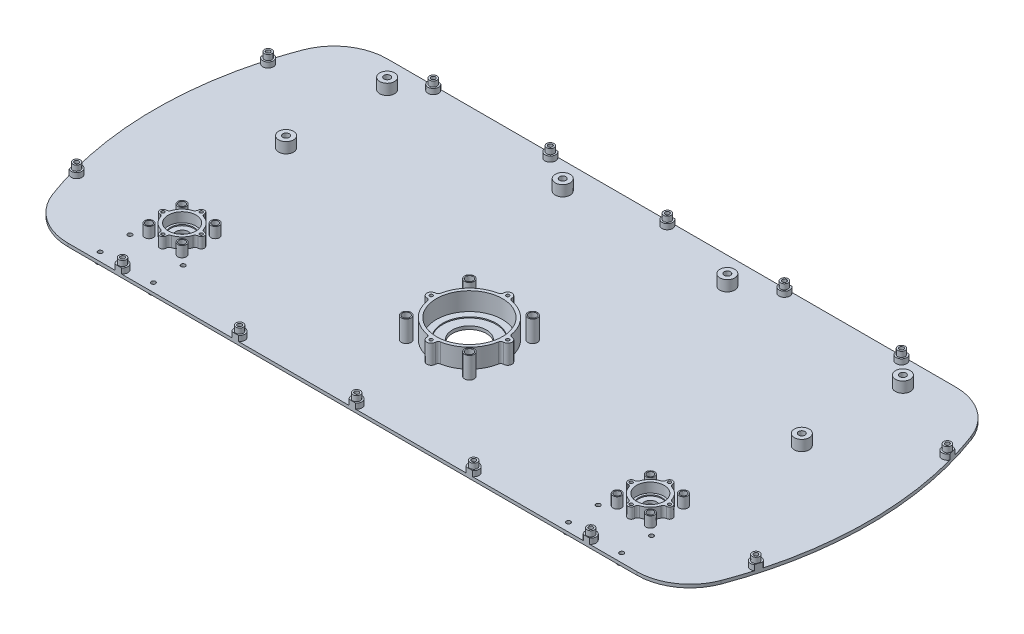
SolidWorks part; units mm, degrees
ref_plane "Front Plane" through (0, 0, 0) normal (0, 0, 1) x (1, 0, 0)
ref_plane "Top Plane" through (0, 0, 0) normal (0, 1, 0) x (1, 0, 0)
ref_plane "Right Plane" through (0, 0, 0) normal (1, 0, 0) x (0, 0, -1)
sketch "Sketch1" plane through (0, 0, 0) normal (0, 1, 0) x (1, 0, 0)
  line L1 (-267.3181, 150) -> (267.3181, 150)
  line L3 (-267.3181, -150) -> (267.3181, -150)
  line L5 (-300, 150) -> (300, -150) construction
  line L6 (-300, -150) -> (300, 150) construction
  arc A0 (314.1486, 117.5186) -> (314.1486, -117.5186) centre (0, 0) cw
  arc A1 (-314.1486, 117.5186) -> (-314.1486, -117.5186) centre (0, 0) ccw
  arc A2 (314.1486, 117.5186) -> (267.3181, 150) centre (267.3181, 100) ccw
  arc A3 (267.3181, -150) -> (314.1486, -117.5186) centre (267.3181, -100) ccw
  arc A4 (-267.3181, -150) -> (-314.1486, -117.5186) centre (-267.3181, -100) cw
  arc A5 (-267.3181, 150) -> (-314.1486, 117.5186) centre (-267.3181, 100) ccw
  circle A6 centre (0, -40) radius 130 construction
  circle A7 centre (-220, -90) radius 60 construction
  circle A8 centre (220, -90) radius 60 construction
  point P0 (0, 0)
  point P19 (0, -40)
  dimension "D3" = 50
  dimension "D5" = 260
  dimension "D6" = 120
  dimension "D7" = 120
  dimension "D1" = 300
  dimension "D2" = 600
  dimension "D4" = 40
  dimension "D8" = 90
  dimension "D9" = 220
  dimension "D10" = 90
  dimension "D11" = 220
extrude "Boss-Extrude1" add sketch "Sketch1" along normal blind 3
sketch "Sketch2" plane through (0, 3, 0) normal (0, 1, 0) x (1, 0, 0)
  circle A0 centre (220, -90) radius 60 construction
  circle A1 centre (-220, -90) radius 60 construction
  circle A2 centre (220, -90) radius 60 construction
  circle A3 centre (-220, -90) radius 60 construction
  circle A4 centre (-220, -90) radius 6
  circle A5 centre (220, -90) radius 6
  circle A6 centre (0, -40) radius 17.5
  circle A7 centre (220, -90) radius 11
  circle A8 centre (220, -90) radius 13
  circle A9 centre (-220, -90) radius 13
  circle A10 centre (-220, -90) radius 11
  circle A13 centre (-220, -90) radius 16
  circle A14 centre (220, -90) radius 16
  circle A15 centre (238, -90) radius 1.5
  arc A16 (235.8611, -87.8964) -> (235.8611, -92.1036) centre (238, -90) cw
  arc A17 (222.1036, -105.8611) -> (217.8964, -105.8611) centre (220, -108) cw
  circle A18 centre (220, -108) radius 1.5
  arc A19 (204.1389, -92.1036) -> (204.1389, -87.8964) centre (202, -90) cw
  circle A20 centre (202, -90) radius 1.5
  arc A21 (217.8964, -74.1389) -> (222.1036, -74.1389) centre (220, -72) cw
  circle A22 centre (220, -72) radius 1.5
  arc A23 (202, -87) -> (204.8114, -84.9696) centre (202, -84.0385) ccw
  arc A24 (202, -93) -> (204.8114, -95.0304) centre (202, -95.9615) cw
  arc A25 (223, -72) -> (225.0304, -74.8114) centre (225.9615, -72) ccw
  arc A26 (217, -72) -> (214.9696, -74.8114) centre (214.0385, -72) cw
  arc A27 (238, -93) -> (235.1886, -95.0304) centre (238, -95.9615) ccw
  arc A28 (238, -87) -> (235.1886, -84.9696) centre (238, -84.0385) cw
  arc A29 (217, -108) -> (214.9696, -105.1886) centre (214.0385, -108) ccw
  arc A30 (223, -108) -> (225.0304, -105.1886) centre (225.9615, -108) cw
  point P36 (220, -90)
  point P61 (220, -90)
  dimension "D1" = 35
  dimension "D2" = 26
  dimension "D3" = 22
  dimension "D4" = 26
  dimension "D5" = 22
  dimension "D6" = 12
  dimension "D7" = 12
  dimension "D8" = 3
  dimension "D9" = 3
  dimension "D10" = 3
  dimension "D11" = 18
  dimension "D12" = 4
  dimension "D13" = 4
extrude "Cut-Extrude1" cut sketch "Sketch2" against normal blind 10 contours A4 | A5 region at (-220, 3, 90) region at (220, 3, 90)
extrude "Boss-Extrude2" add sketch "Sketch2<3>" along normal blind 1 from surface contours A9 A10 | A8 A7 region at (207.3677, 3, 90) region at (-232.6323, 3, 90) starting at face at (-220, 3, 96)
sketch "Sketch2<3>" plane through (0, 3, 0) normal (0, 1, 0) x (1, 0, 0) same geometry as "Sketch2"
extrude "Boss-Extrude3" add sketch "Sketch2<4>" along normal blind 10 from surface contours A14 A8 | A19 A14 A20 | A21 A14 A22 | A16 A14 A15 | A17 A14 A18 | A23 A19 A14 | A19 A24 A14 | A25 A21 A14 | A21 A26 A14 | A16 A28 A14 | A27 A16 A14 | A17 A30 A14 | A29 A17 A14 region at (235.5137, 3, 91.0243) region at (236.0441, 3, 88.9407) region at (236.2045, 3, 86.846) region at (236.2045, 3, 93.154) region at (223.154, 3, 73.7955) region at (223.154, 3, 106.2045) region at (220, 3, 73.921) region at (222.694, 3, 106.871) region at (216.846, 3, 73.7955) region at (216.846, 3, 106.2045) region at (203.7955, 3, 86.846) region at (203.7955, 3, 93.154) region at (203.921, 3, 90) starting at face at (220, 3, 103)
sketch "Sketch2<4>" plane through (0, 3, 0) normal (0, 1, 0) x (1, 0, 0) same geometry as "Sketch2"
sketch "Sketch3" plane through (0, 3, 0) normal (0, 1, 0) x (1, 0, 0)
  circle A0 centre (0, -40) radius 16
  circle A1 centre (0, -40) radius 25
  circle A2 centre (0, -40) radius 31
  circle A3 centre (0, -40) radius 34
  circle A4 centre (36, -40) radius 1.5
  arc A6 (33.8333, -43.3624) -> (33.8333, -36.6376) centre (36, -40) ccw
  arc A7 (-3.3624, -73.8333) -> (3.3624, -73.8333) centre (0, -76) ccw
  circle A8 centre (0, -76) radius 1.5
  arc A9 (-33.8333, -36.6376) -> (-33.8333, -43.3624) centre (-36, -40) ccw
  circle A10 centre (-36, -40) radius 1.5
  arc A11 (3.3624, -6.1667) -> (-3.3624, -6.1667) centre (0, -4) ccw
  circle A12 centre (0, -4) radius 1.5
  arc A13 (-36, -36) -> (-33.4426, -33.8689) centre (-36, -33.4) ccw
  arc A14 (-36, -44) -> (-33.4426, -46.1311) centre (-36, -46.6) cw
  arc A15 (4, -4) -> (6.1311, -6.5574) centre (6.6, -4) ccw
  arc A16 (-4, -4) -> (-6.1311, -6.5574) centre (-6.6, -4) cw
  arc A17 (36, -44) -> (33.4426, -46.1311) centre (36, -46.6) ccw
  arc A18 (36, -36) -> (33.4426, -33.8689) centre (36, -33.4) cw
  arc A19 (-4, -76) -> (-6.1311, -73.4426) centre (-6.6, -76) ccw
  arc A20 (4, -76) -> (6.1311, -73.4426) centre (6.6, -76) cw
  point P25 (0, -40)
  point P50 (0, -40)
  dimension "D1" = 32
  dimension "D2" = 62
  dimension "D3" = 3
  dimension "D4" = 50
  dimension "D5" = 4
  dimension "D7" = 3
  dimension "D6" = 36
  dimension "D8" = 4
  dimension "D9" = 4
extrude "Cut-Extrude8" cut sketch "Sketch3" against normal blind 10 contours A0 region at (0, 3, 40)
extrude "Boss-Extrude4" add sketch "Sketch3<3>" along normal blind 1 from surface contours A2 A1 region at (-30.1232, 3, 40) starting at face at (0, 3, 56)
sketch "Sketch3<3>" plane through (0, 3, 0) normal (0, 1, 0) x (1, 0, 0) same geometry as "Sketch3"
extrude "Boss-Extrude5" add sketch "Sketch3<4>" along normal blind 18 from surface contours A3 A2 | A3 A6 A4 | A3 A7 A8 | A3 A9 A10 | A3 A11 A12 | A13 A9 A3 | A9 A14 A3 | A11 A16 A3 | A15 A11 A3 | A17 A6 A3 | A6 A18 A3 | A7 A20 A3 | A19 A7 A3 region at (32.9978, 3, 41.6356) region at (34.0592, 3, 38.3117) region at (34.2416, 3, 35.7431) region at (34.2416, 3, 44.2569) region at (4.2569, 3, 5.7584) region at (4.2569, 3, 74.2416) region at (0, 3, 5.899) region at (3.7404, 3, 74.8992) region at (-4.2569, 3, 5.7584) region at (-4.2569, 3, 74.2416) region at (-34.2416, 3, 35.7431) region at (-34.2416, 3, 44.2569) region at (-34.101, 3, 40) starting at face at (0, 3, 71)
sketch "Sketch3<4>" plane through (0, 3, 0) normal (0, 1, 0) x (1, 0, 0) same geometry as "Sketch3"
mirror "Mirror1" about plane through (0, 0, 0) normal (1, 0, 0) of "Boss-Extrude3"
sketch "Sketch4" plane through (0, 3, 0) normal (0, 1, 0) x (1, 0, 0)
  line B0 (0, -40) -> (-78.0469, 38.0469) construction
  circle B1 centre (-29.6985, -10.3015) radius 2
  circle B2 centre (-29.6985, -10.3015) radius 4.5
  circle B3 centre (-29.6985, -10.3015) radius 3.5
  circle B4 centre (29.6985, -10.3015) radius 4.5
  circle B5 centre (29.6985, -10.3015) radius 3.5
  circle B6 centre (29.6985, -10.3015) radius 2
  circle B7 centre (29.6985, -69.6985) radius 4.5
  circle B8 centre (29.6985, -69.6985) radius 3.5
  circle B9 centre (29.6985, -69.6985) radius 2
  circle B10 centre (-29.6985, -69.6985) radius 4.5
  circle B11 centre (-29.6985, -69.6985) radius 3.5
  circle B12 centre (-29.6985, -69.6985) radius 2
  circle B13 centre (-29.6985, -10.3015) radius 6.5
  arc B14 (-31.7007, -27.4352) -> (-34.2947, -14.8977) centre (-42.5371, -23.1401) ccw
  arc B15 (-12.5648, -8.2993) -> (-25.1023, -5.7053) centre (-16.8599, 2.5371) cw
  arc B16 (12.5648, -8.2993) -> (25.1023, -5.7053) centre (16.8599, 2.5371) ccw
  arc B17 (31.7007, -27.4352) -> (34.2947, -14.8977) centre (42.5371, -23.1401) cw
  circle B18 centre (29.6985, -10.3015) radius 6.5
  arc B19 (31.7007, -52.5648) -> (34.2947, -65.1023) centre (42.5371, -56.8599) ccw
  arc B20 (12.5648, -71.7007) -> (25.1023, -74.2947) centre (16.8599, -82.5371) cw
  circle B21 centre (29.6985, -69.6985) radius 6.5
  arc B22 (-12.5648, -71.7007) -> (-25.1023, -74.2947) centre (-16.8599, -82.5371) ccw
  arc B23 (-31.7007, -52.5648) -> (-34.2947, -65.1023) centre (-42.5371, -56.8599) cw
  circle B24 centre (-29.6985, -69.6985) radius 6.5
  circle B25 centre (0, -40) radius 34.1
  circle B26 centre (3.6047, -60.6883) radius 2.7
  circle B27 centre (-19.7189, -32.7776) radius 2.7
  circle B28 centre (16.1143, -26.5341) radius 2.7
  circle B29 centre (0, -40) radius 6.5
sketch_block_instance "Block2-1"
sketch_block "Block2" parameters "D1"=4, "D2"=7, "D3"=9, "D4"=13
sketch_block_instance "Block1-1"
sketch_block "Block1"
extrude "Boss-Extrude6" add sketch "Sketch4" along normal blind 20 contours B4 B5 | B5 B6 | B2 B3 | B3 B1 | B7 B8 | B8 B9 | B10 B11 | B11 B12 region at (-34.0712, 3, 10.3015) region at (-33.0995, 3, 10.3015) region at (25.3258, 3, 10.3015) region at (26.2975, 3, 10.3015) region at (25.3258, 3, 69.6985) region at (26.2975, 3, 69.6985) region at (-34.0712, 3, 69.6985) region at (-33.0995, 3, 69.6985)
extrude "Cut-Extrude9" cut sketch "Sketch4<3>" against normal blind 5 from surface contours B3 B1 | B5 B6 | B8 B9 | B11 B12 region at (-33.0995, 3, 10.3015) region at (26.2975, 3, 10.3015) region at (26.2975, 3, 69.6985) region at (-33.0995, 3, 69.6985) starting at face at (-29.6985, 23, 14.8015)
sketch "Sketch4<3>" plane through (0, 3, 0) normal (0, 1, 0) x (1, 0, 0) same geometry as "Sketch4"
sketch "Sketch5" plane through (0, 3, 0) normal (0, 1, 0) x (1, 0, 0)
  circle B0 centre (204.4437, -74.4437) radius 1.5
  circle B1 centre (204.4437, -74.4437) radius 3
  circle B2 centre (204.4437, -74.4437) radius 4
  circle B3 centre (204.4437, -105.5563) radius 1.5
  arc B4 (200.5546, -101.6673) -> (208.3327, -109.4454) centre (204.4437, -105.5563) ccw
  arc B5 (218.4477, -105.824) -> (208.3327, -109.4454) centre (217.2205, -118.3332) ccw
  arc B6 (218.4477, -105.824) -> (221.5523, -105.824) centre (220, -90) ccw
  arc B7 (231.6673, -109.4454) -> (221.5523, -105.824) centre (222.7795, -118.3332) ccw
  arc B8 (231.6673, -109.4454) -> (239.4454, -101.6673) centre (235.5563, -105.5563) ccw
  arc B9 (235.824, -91.5523) -> (239.4454, -101.6673) centre (248.3332, -92.7795) ccw
  arc B10 (235.824, -91.5523) -> (235.824, -88.4477) centre (220, -90) ccw
  arc B11 (239.4454, -78.3327) -> (235.824, -88.4477) centre (248.3332, -87.2205) ccw
  arc B12 (239.4454, -78.3327) -> (231.6673, -70.5546) centre (235.5563, -74.4437) ccw
  arc B13 (221.5523, -74.176) -> (231.6673, -70.5546) centre (222.7795, -61.6668) ccw
  arc B14 (221.5523, -74.176) -> (218.4477, -74.176) centre (220, -90) ccw
  arc B15 (208.3327, -70.5546) -> (218.4477, -74.176) centre (217.2205, -61.6668) ccw
  arc B16 (208.3327, -70.5546) -> (200.5546, -78.3327) centre (204.4437, -74.4437) ccw
  arc B17 (204.176, -88.4477) -> (200.5546, -78.3327) centre (191.6668, -87.2205) ccw
  arc B18 (204.176, -88.4477) -> (204.176, -91.5523) centre (220, -90) ccw
  arc B19 (200.5546, -101.6673) -> (204.176, -91.5523) centre (191.6668, -92.7795) ccw
  circle B20 centre (204.4437, -105.5563) radius 3
  circle B21 centre (204.4437, -105.5563) radius 4
  circle B22 centre (235.5563, -105.5563) radius 1.5
  circle B23 centre (235.5563, -105.5563) radius 3
  circle B24 centre (235.5563, -105.5563) radius 4
  circle B25 centre (235.5563, -74.4437) radius 1.5
  circle B26 centre (235.5563, -74.4437) radius 3
  circle B27 centre (235.5563, -74.4437) radius 4
sketch_block_instance "Block3-1"
sketch_block "Block3"
extrude "Boss-Extrude7" add sketch "Sketch5" along normal blind 10 contours B27 B26 | B26 B25 | B2 B1 | B1 B0 | B24 B23 | B23 B22 | B20 B3 | B21 B20 region at (201.5285, 3, 74.4437) region at (200.5568, 3, 74.4437) region at (201.5285, 3, 105.5563) region at (200.5568, 3, 105.5563) region at (232.6412, 3, 105.5563) region at (231.6695, 3, 105.5563) region at (232.6412, 3, 74.4437) region at (231.6695, 3, 74.4437)
extrude "Cut-Extrude10" cut sketch "Sketch5<3>" against normal blind 5 from surface contours B20 B3 | B1 B0 | B26 B25 | B23 B22 region at (201.5285, 3, 74.4437) region at (201.5285, 3, 105.5563) region at (232.6412, 3, 105.5563) region at (232.6412, 3, 74.4437) starting at face at (235.5563, 13, 109.5563)
sketch "Sketch5<3>" plane through (0, 3, 0) normal (0, 1, 0) x (1, 0, 0) same geometry as "Sketch5"
mirror "Mirror2" about plane through (0, 0, 0) normal (1, 0, 0) of "Boss-Extrude7", "Cut-Extrude10"
sketch "Sketch7" plane through (0, 0, 0) normal (0, -1, 0) x (1, 0, 0)
  line B0 (220, 61) -> (-220, 61)
  line B1 (220, 119) -> (-220, 119)
  line B2 (220, 121) -> (-220, 121)
  line B3 (220, 59) -> (-220, 59)
  arc B4 (220, 119) -> (220, 61) centre (220, 90) cw
  arc B5 (-220, 119) -> (-220, 61) centre (-220, 90) ccw
  arc B6 (-220, 121) -> (-220, 59) centre (-220, 90) ccw
  arc B7 (220, 121) -> (220, 59) centre (220, 90) cw
  circle B8 centre (0, 115.25) radius 2
  circle B9 centre (0, 64.75) radius 2
  arc B10 (-3.3072, 119) -> (3.3072, 119) centre (0, 115.25) ccw
  arc B11 (-3.3072, 61) -> (3.3072, 61) centre (0, 64.75) cw
  circle B12 centre (0, 115.25) radius 3.5
  circle B13 centre (0, 64.75) radius 3.5
sketch_block_instance "Block5-1"
sketch_block "Block5" parameters "D4"=4, "D7"=4, "D1"=440, "D2"=29, "D3"=29, "D5"=7, "D6"=3, "D8"=8.5, "D9"=3.75, "D10"=8.5, "D11"=3.75, "D12"=2
sketch "Sketch8" plane through (0, 0, 0) normal (0, -1, 0) x (1, 0, 0)
  line L0 (-267.3181, 150) -> (267.3181, 150) construction
  circle B0 centre (-245, 114) radius 4.525
  circle B1 centre (-245, 142) radius 4.525
  circle B2 centre (-195, 142) radius 3.525
  circle B3 centre (-195, 142) radius 2
  circle B4 centre (-195, 142) radius 4.525
  circle B5 centre (-195, 114) radius 4.525
  circle B6 centre (-195, 114) radius 3.525
  circle B7 centre (-195, 114) radius 2
  circle B8 centre (-245, 114) radius 2
  circle B9 centre (-245, 114) radius 3.525
  circle B10 centre (-245, 142) radius 2
  circle B11 centre (-245, 142) radius 3.525
  dimension "D1" = 8
sketch_block_instance "Block7-1"
sketch_block "Block7" parameters "D1"=25, "D2"=14
sketch_block_instance "Block6-1"
sketch_block "Block6"
extrude "Boss-Extrude8" add sketch "Sketch8" along normal blind 5 contours B11 B10 | B2 B3 | B6 B7 | B9 B8 region at (-198.4253, 0, 142) region at (-198.4253, 0, 114) region at (-248.4253, 0, 114) region at (-248.4253, 0, 142)
extrude "Cut-Extrude11" cut sketch "Sketch8<3>" against normal blind 10 contours B3 | B7 | B8 | B10 region at (-195, 0, 142) region at (-195, 0, 114) region at (-245, 0, 114) region at (-245, 0, 142)
sketch "Sketch8<3>" plane through (0, 0, 0) normal (0, -1, 0) x (1, 0, 0) same geometry as "Sketch8"
mirror "Mirror3" about plane through (0, 0, 0) normal (1, 0, 0) of "Cut-Extrude11", "Boss-Extrude8"
sketch "Sketch9" plane through (0, 0, 0) normal (0, -1, 0) x (1, 0, 0)
  line L0 (-267.3181, 150) -> (267.3181, 150) construction
  line L1 (-267.3181, -150) -> (267.3181, -150) construction
  line L2 (-267.3181, 150) -> (267.3181, 150)
  line L3 (-267.3181, -150) -> (267.3181, -150)
  arc A0 (314.1486, 117.5186) -> (267.3181, 150) centre (267.3181, 100) ccw construction
  arc A1 (314.1486, -117.5186) -> (314.1486, 117.5186) centre (0, 0) ccw construction
  arc A2 (267.3181, -150) -> (314.1486, -117.5186) centre (267.3181, -100) ccw construction
  arc A3 (-314.1486, -117.5186) -> (-267.3181, -150) centre (-267.3181, -100) ccw construction
  arc A4 (-314.1486, 117.5186) -> (-314.1486, -117.5186) centre (0, 0) ccw construction
  arc A5 (-267.3181, 150) -> (-314.1486, 117.5186) centre (-267.3181, 100) ccw construction
  arc A6 (314.1486, 117.5186) -> (267.3181, 150) centre (267.3181, 100) ccw
  arc A7 (314.1486, -117.5186) -> (314.1486, 117.5186) centre (0, 0) ccw
  arc A8 (267.3181, -150) -> (314.1486, -117.5186) centre (267.3181, -100) ccw
  arc A9 (-314.1486, -117.5186) -> (-267.3181, -150) centre (-267.3181, -100) ccw
  arc A10 (-314.1486, 117.5186) -> (-314.1486, -117.5186) centre (0, 0) ccw
  arc A11 (-267.3181, 150) -> (-314.1486, 117.5186) centre (-267.3181, 100) ccw
  circle A12 centre (0, -146) radius 2
  circle A13 centre (0, -146) radius 3.5
  circle A14 centre (0, -146) radius 5
  circle A15 centre (319.1486, -90) radius 2
  circle A16 centre (319.1486, -90) radius 3.5
  circle A17 centre (319.1486, -90) radius 5
  dimension "D1" = 4
  dimension "D2" = 1.5
  dimension "D3" = 1.5
  dimension "D5" = 4
  dimension "D6" = 1.5
  dimension "D7" = 1.5
  dimension "D9" = 5
  dimension "D4" = 4
  dimension "D8" = 60
extrude "Cut-Extrude12" cut sketch "Sketch9" against normal blind 10 contours A12 region at (0, 0, -146)
extrude "Boss-Extrude9" add sketch "Sketch9<3>" against normal blind 10 from surface contours A13 A12 region at (-3.401, 0, -146) starting at face at (0, 3, -144)
sketch "Sketch9<3>" plane through (0, 0, 0) normal (0, -1, 0) x (1, 0, 0) same geometry as "Sketch9"
pattern_linear "LPattern1" count 3 spacing 110 along (1, 0, 0) of "Cut-Extrude12", "Boss-Extrude9"
pattern_linear "LPattern2" count 3 spacing 110 along (-1, 0, 0) of "Cut-Extrude12", "Boss-Extrude9"
mirror "Mirror4" about plane through (0, 0, 0) normal (0, 0, 1) of "LPattern2", "LPattern1"
extrude "Cut-Extrude13" cut sketch "Sketch9<5>" against normal blind 10 contours A15 region at (319.1486, 0, -90)
sketch "Sketch9<5>" plane through (0, 0, 0) normal (0, -1, 0) x (1, 0, 0) same geometry as "Sketch9"
extrude "Boss-Extrude10" add sketch "Sketch9<6>" against normal blind 10 from surface contours A16 A15 region at (315.7476, 0, -90) starting at face at (319.1486, 3, -88)
sketch "Sketch9<6>" plane through (0, 0, 0) normal (0, -1, 0) x (1, 0, 0) same geometry as "Sketch9"
mirror "Mirror9" about plane through (0, 0, 0) normal (0, 0, 1) of "Boss-Extrude10", "Cut-Extrude13" second plane through (0, 0, 0) second plane normal (1, 0, 0)
extrude "Boss-Extrude11" add sketch "Sketch9<7>" against normal blind 5 from surface contours L3 A14 A13 region at (-2.1759, 0, -141.6482) starting at face at (-319.1486, 3, 86.5)
sketch "Sketch9<7>" plane through (0, 0, 0) normal (0, -1, 0) x (1, 0, 0) same geometry as "Sketch9"
pattern_linear "LPattern3" count 3 spacing 110 along (1, 0, 0) of "Boss-Extrude11"
pattern_linear "LPattern4" count 3 spacing 110 along (-1, 0, 0) of "LPattern3"
mirror "Mirror10" about plane through (0, 0, 0) normal (0, 0, 1) of "Boss-Extrude11", "LPattern3", "LPattern4"
extrude "Boss-Extrude12" add sketch "Sketch9<8>" against normal blind 5 from surface contours A7 A17 A16 region at (322.6867, 0, -90.9977) starting at face at (-319.1486, 3, 86.5)
sketch "Sketch9<8>" plane through (0, 0, 0) normal (0, -1, 0) x (1, 0, 0) same geometry as "Sketch9"
mirror "Mirror18" about plane through (0, 0, 0) normal (1, 0, 0) of "Boss-Extrude12"
mirror "Mirror19" about plane through (0, 0, 0) normal (0, 0, 1) of "Mirror18"
sketch "Sketch10" plane through (0, 3, 0) normal (0, 1, 0) x (1, 0, 0)
  line L0 (-267.3181, 150) -> (267.3181, 150) construction
  line L1 (-267.3181, -150) -> (267.3181, -150) construction
  line L2 (-267.3181, 150) -> (267.3181, 150)
  line L3 (-267.3181, -150) -> (267.3181, -150)
  circle A0 centre (-220, -146) radius 2 construction
  circle A1 centre (-220, -146) radius 3.5 construction
  arc A2 (-217, -150) -> (-223, -150) centre (-220, -146) ccw construction
  circle A3 centre (-319.1486, 90) radius 2 construction
  circle A4 centre (-319.1486, 90) radius 3.5 construction
  arc A5 (-323.687, 87.9017) -> (-321.9221, 94.1603) centre (-319.1486, 90) ccw construction
  circle A6 centre (-220, 146) radius 2 construction
  circle A7 centre (-220, 146) radius 3.5 construction
  arc A8 (-223, 150) -> (-217, 150) centre (-220, 146) ccw construction
  arc A9 (314.1486, 117.5186) -> (267.3181, 150) centre (267.3181, 100) ccw construction
  arc A10 (314.1486, -117.5186) -> (314.1486, 117.5186) centre (0, 0) ccw construction
  arc A11 (267.3181, -150) -> (314.1486, -117.5186) centre (267.3181, -100) ccw construction
  arc A12 (-314.1486, -117.5186) -> (-267.3181, -150) centre (-267.3181, -100) ccw construction
  arc A13 (-314.1486, 117.5186) -> (-314.1486, -117.5186) centre (0, 0) ccw construction
  arc A14 (-267.3181, 150) -> (-314.1486, 117.5186) centre (-267.3181, 100) ccw construction
  circle A15 centre (-220, -146) radius 2
  circle A16 centre (-220, -146) radius 3.5
  arc A17 (-217, -150) -> (-223, -150) centre (-220, -146) ccw
  circle A18 centre (-319.1486, 90) radius 2
  circle A19 centre (-319.1486, 90) radius 3.5
  arc A20 (-323.687, 87.9017) -> (-321.9221, 94.1603) centre (-319.1486, 90) ccw
  circle A21 centre (-220, 146) radius 2
  circle A22 centre (-220, 146) radius 3.5
  arc A23 (-223, 150) -> (-217, 150) centre (-220, 146) ccw
  arc A24 (314.1486, 117.5186) -> (267.3181, 150) centre (267.3181, 100) ccw
  arc A25 (314.1486, -117.5186) -> (314.1486, 117.5186) centre (0, 0) ccw
  arc A26 (267.3181, -150) -> (314.1486, -117.5186) centre (267.3181, -100) ccw
  arc A27 (-314.1486, -117.5186) -> (-267.3181, -150) centre (-267.3181, -100) ccw
  arc A28 (-314.1486, 117.5186) -> (-314.1486, -117.5186) centre (0, 0) ccw
  arc A29 (-267.3181, 150) -> (-314.1486, 117.5186) centre (-267.3181, 100) ccw
sketch "Sketch11" plane through (0, 3, 0) normal (0, 1, 0) x (1, 0, 0)
  circle A0 centre (-242.3181, 125) radius 5
  circle A1 centre (-242.3181, 125) radius 3
  circle A2 centre (-242.3181, 125) radius 7
  point P4 (-238.0513, 167.9788)
  point P6 (-237.1072, 138.2844)
  dimension "D1" = 6
  dimension "D2" = 2
  dimension "D3" = 2
  dimension "D4" = 25
  dimension "D5" = 25
extrude "Cut-Extrude14" cut sketch "Sketch11" against normal blind 10 contours A1 region at (-242.3181, 3, -125)
extrude "Boss-Extrude13" add sketch "Sketch11<3>" along normal blind 10 contours A0 A1 | A2 A0 region at (-247.1767, 3, -125) region at (-249.1201, 3, -125)
sketch "Sketch11<3>" plane through (0, 3, 0) normal (0, 1, 0) x (1, 0, 0) same geometry as "Sketch11"
pattern_linear "LPattern5" count 2 spacing 165 along (1, 0, 0) of "Cut-Extrude14", "Boss-Extrude13"
mirror "Mirror20" about plane through (0, 0, 0) normal (1, 0, 0) of "LPattern5"
pattern_linear "LPattern6" count 2 spacing 95 along (0, 0, 1) of "Cut-Extrude14", "Boss-Extrude13"
mirror "Mirror21" about plane through (0, 0, 0) normal (1, 0, 0) of "LPattern6"
